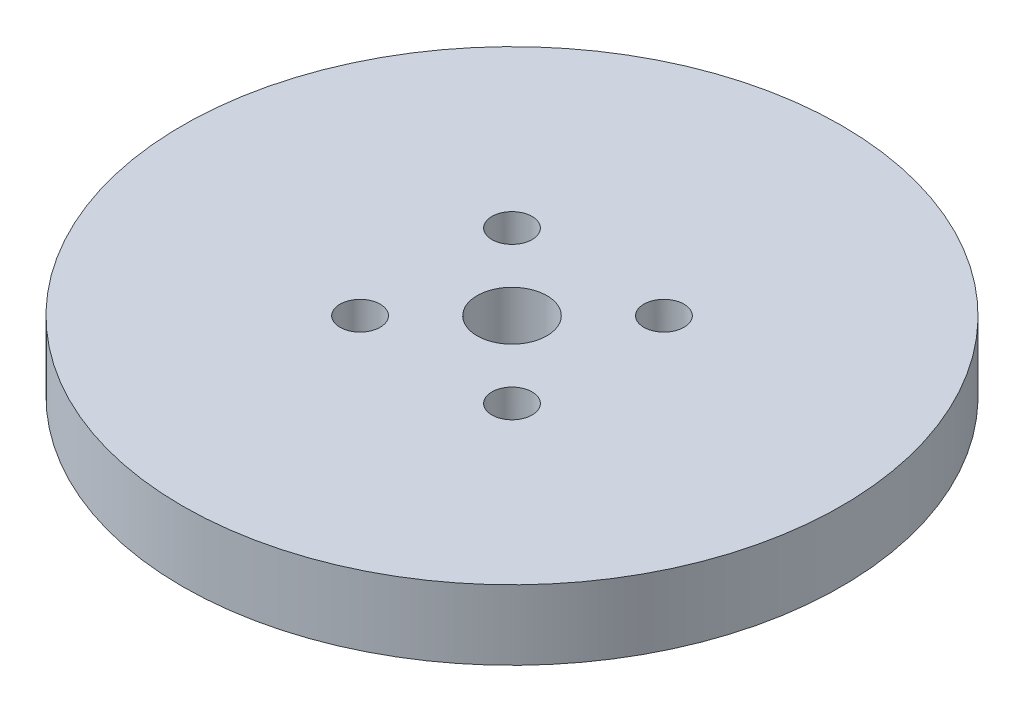
SolidWorks part; units mm, degrees
material "ABS"
ref_plane "Plan de face" through (0, 0, 0) normal (0, 0, 1) x (1, 0, 0)
ref_plane "Plan de dessus" through (0, 0, 0) normal (0, 1, 0) x (1, 0, 0)
ref_plane "Plan de droite" through (0, 0, 0) normal (1, 0, 0) x (0, 0, -1)
sketch "Esquisse1" plane through (0, 0, 0) normal (0, 1, 0) x (1, 0, 0)
  circle A0 centre (0, 0) radius 30
  dimension "D1" = 60
extrude "Boss.-Extru.1" add sketch "Esquisse1" along normal blind 6.35
sketch "Esquisse2" plane through (0, 6.35, 0) normal (0, 1, 0) x (1, 0, 0)
  circle A0 centre (0, 0) radius 3.175
  dimension "D1" = 6.35
extrude "Enlèv. mat.-Extru.1" cut sketch "Esquisse2" against normal up to next
sketch "Sketch1" plane through (0, 6.35, 0) normal (0, 1, 0) x (1, 0, 0)
  circle A0 centre (-6.9148, -6.9148) radius 1.8288
  circle A2 centre (-6.9148, -6.9148) radius 2.8702 construction
  point P2 (0, 0)
  point P5 (0, 0)
  dimension "D1" = 3.6576
  dimension "D2" = 0
extrude "Cut-Extrude1" cut sketch "Sketch1" against normal up to surface (6.35 mm away) up to face at (0, 0, 3.175)
ref_axis "Axis1" through (0, -0.3175, 0) along (0, 1, 0)
pattern_circular "CirPattern1" count 4 every 90 about axis through (0, -0.3175, 0) along (0, 1, 0) of "Cut-Extrude1"
